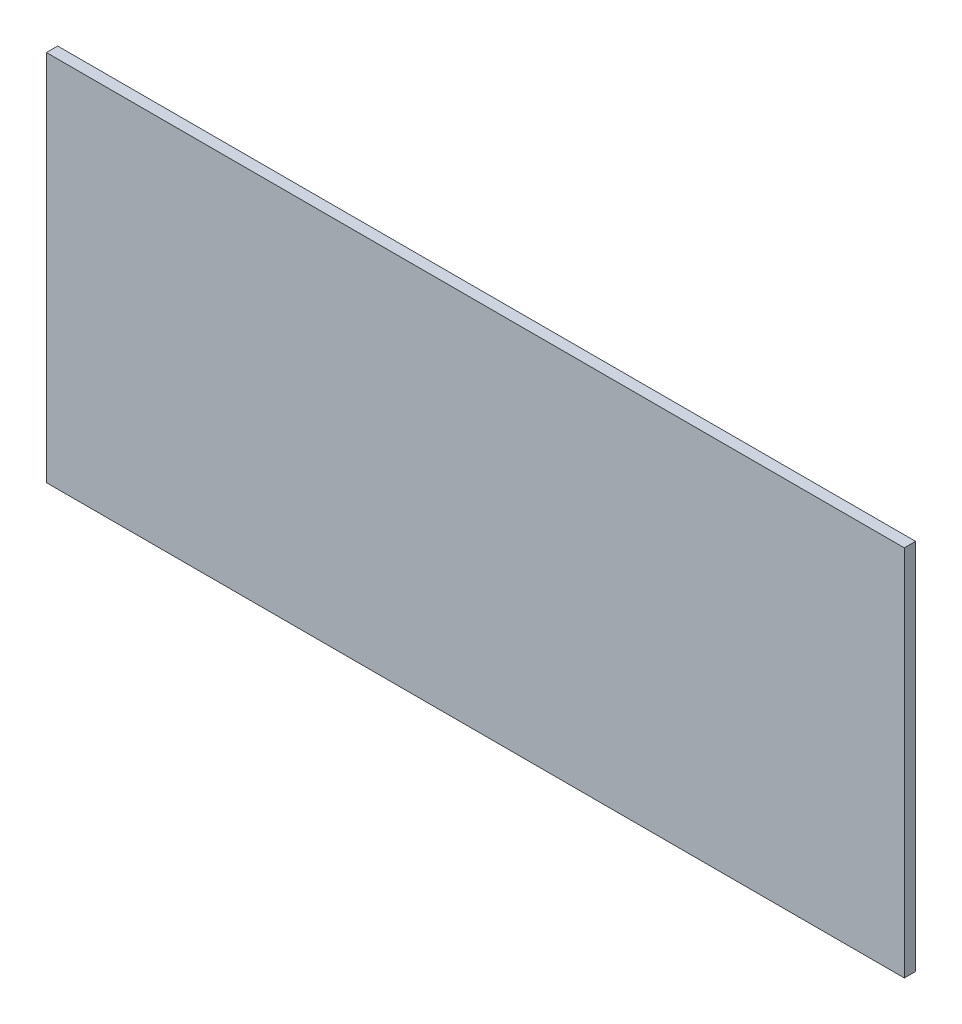
SolidWorks part; units mm, degrees
ref_plane "Plan de face" through (0, 0, 0) normal (0, 0, 1) x (1, 0, 0)
ref_plane "Plan de dessus" through (0, 0, 0) normal (0, 1, 0) x (1, 0, 0)
ref_plane "Plan de droite" through (0, 0, 0) normal (1, 0, 0) x (0, 0, -1)
sketch "Esquisse1" plane through (0, 0, 0) normal (0, 0, 1) x (1, 0, 0)
  line L1 (-208.4671, 51.8304) -> (171.5329, 51.8304)
  line L2 (-208.4671, 51.8304) -> (-208.4671, -113.1696)
  line L3 (-208.4671, -113.1696) -> (171.5329, -113.1696)
  line L4 (171.5329, 51.8304) -> (171.5329, -113.1696)
  dimension "D1" = 380
  dimension "D2" = 165
extrude "Boss.-Extru.1" add sketch "Esquisse1" along normal blind 5
